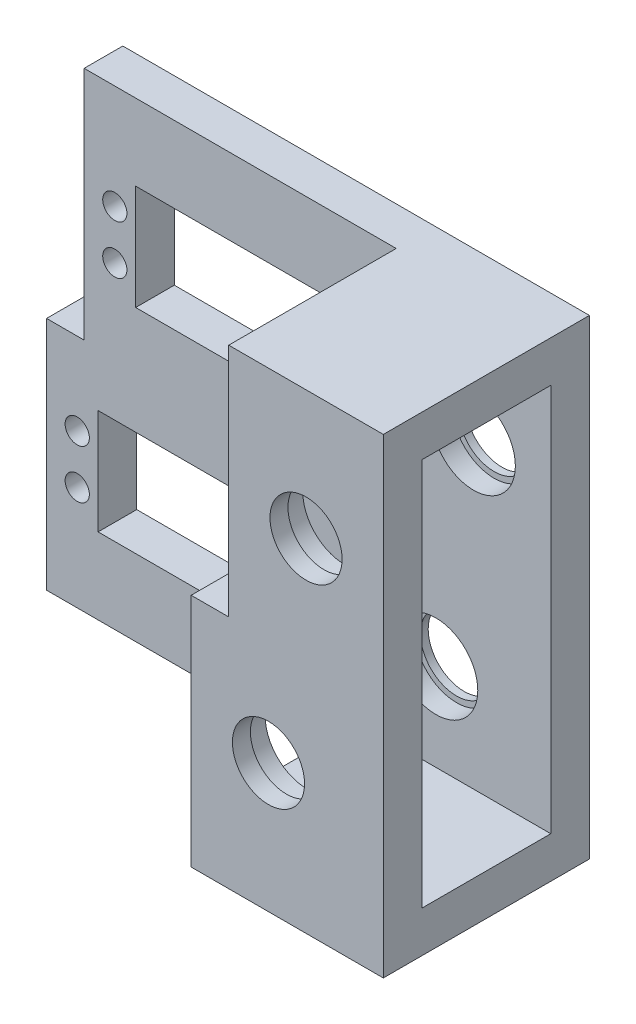
SolidWorks part; units mm, degrees
ref_plane "Front Plane" through (0, 0, 0) normal (0, 0, 1) x (1, 0, 0)
ref_plane "Top Plane" through (0, 0, 0) normal (0, 1, 0) x (1, 0, 0)
ref_plane "Right Plane" through (0, 0, 0) normal (1, 0, 0) x (0, 0, -1)
sketch "Sketch1" plane through (0, 0, 0) normal (0, 0, 1) x (1, 0, 0)
  line L0 (-15, 0) -> (22.2932, 0)
  line L5 (-15, 91.3619) -> (22.2932, 91.3619)
  line L6 (-15, 0) -> (-15, 91.3619)
  line L7 (22.2932, 0) -> (22.2932, 91.3619)
  line L8 (0, 25) -> (7.2932, 66.3619) construction
  line L9 (0, 25) -> (0, 79.2) construction
  circle A1 centre (0, 25) radius 8.125
  circle A2 centre (7.2932, 66.3619) radius 8.125
  point P0 (-15, 0)
  point P4 (0, 0)
  dimension "D2" = 16.25
  dimension "D5" = 25
  dimension "D4" = 15
  dimension "D6" = 25
  dimension "D8" = 42
  dimension "D9" = 10
  dimension "D10" = 15
extrude "Boss-Extrude1" add sketch "Sketch1" along normal blind 40
sketch "Sketch2" plane through (0, 0, 0) normal (0, 1, 0) x (1, 0, 0)
  line L1 (-15, -7.5) -> (22.2932, -7.5)
  line L2 (-15, -7.5) -> (-15, -32.5)
  line L3 (-15, -32.5) -> (22.2932, -32.5)
  line L4 (22.2932, -7.5) -> (22.2932, -32.5)
  line L6 (-15, -40) -> (-15, 0) construction
  line L7 (22.2932, -40) -> (22.2932, 0) construction
  point P4 (-15, -7.5)
  point P6 (22.2932, -32.5)
  point P8 (22.2932, -33.1865)
  point P9 (22.2932, -20)
  point P10 (22.2932, -20)
  point P12 (-15, -7.5)
  point P14 (-15, -7.5)
  point P15 (0, 0)
  point P17 (22.2932, -32.5)
  dimension "D1" = 25
extrude "Cut-Extrude1" cut sketch "Sketch2" along normal through all from offset 8
sketch "Sketch10" plane through (0, 0, 40) normal (0, 0, 1) x (1, 0, 0)
  circle A0 centre (7.2932, 66.3619) radius 8.125
  circle A1 centre (0, 25) radius 10.837
  circle A2 centre (7.2932, 66.3619) radius 7
  circle A3 centre (0, 25) radius 7
  circle A4 centre (7.2932, 66.3619) radius 8.125 construction
  circle A5 centre (0, 25) radius 8.125 construction
  dimension "D2" = 14
  dimension "D4" = 14
extrude "Boss-Extrude2" add sketch "Sketch10" against normal offset from surface (3.5 mm away) 4 up to face at (-8.125, 25, 32.5)
sketch "Sketch11" plane through (0, 0, 0) normal (0, 0, -1) x (-1, 0, 0)
  circle A0 centre (-7.2932, 66.3619) radius 8.125
  circle A1 centre (-7.2932, 66.3619) radius 7
  circle A2 centre (0, 25) radius 8.125
  circle A3 centre (0, 25) radius 7
  circle A4 centre (0, 25) radius 8.125 construction
  circle A5 centre (-7.2932, 66.3619) radius 8.125 construction
  dimension "D1" = 14
  dimension "D2" = 14
extrude "Boss-Extrude3" add sketch "Sketch11" against normal offset from surface (3.5 mm away) 4 up to face at (8.125, 25, 7.5)
ref_axis "Axis1" through (0, 25, 3.5) along (0, 0, -1)
ref_plane "Plane1" through (0, 25, 0) normal (0, -1, 0) x (-1, 0, 0)
ref_axis "Axis2" through (7.2932, 66.3619, 3.5) along (0, 0, -1)
ref_plane "Plane2" through (0, 66.3619, 0) normal (0, -1, 0) x (-1, 0, 0)
sketch "Sketch12" plane through (0, 0, 0) normal (0, 0, -1) x (-1, 0, 0)
  line L0 (-22, 25) -> (22, 25) construction
  line L1 (15, 0) -> (75.56, 0)
  line L2 (15, 0) -> (15, 91.3619)
  line L3 (15, 91.3619) -> (68.2668, 91.3619)
  line L5 (-22, 66.3619) -> (22, 66.3619) construction
  line L6 (24.66, 35.2) -> (65.56, 35.2)
  line L7 (24.66, 35.2) -> (24.66, 14.8)
  line L8 (24.66, 14.8) -> (65.56, 14.8)
  line L9 (65.56, 35.2) -> (65.56, 14.8)
  line L10 (-22.2932, 91.3619) -> (15, 91.3619) construction
  line L11 (17.3668, 76.5619) -> (58.2668, 76.5619)
  line L12 (17.3668, 76.5619) -> (17.3668, 56.1619)
  line L13 (17.3668, 56.1619) -> (58.2668, 56.1619)
  line L14 (58.2668, 76.5619) -> (58.2668, 56.1619)
  line L16 (15, 0) -> (-22.2932, 0) construction
  line L17 (15, 91.3619) -> (15, 0) construction
  line L18 (68.2668, 91.3619) -> (68.2668, 45.681)
  line L19 (68.2668, 45.681) -> (75.56, 45.681)
  line L20 (75.56, 45.681) -> (75.56, 0)
  line L21 (58.2668, 56.1619) -> (58.2668, 35.2) construction
  circle A0 centre (35, 25) radius 6.6 construction
  circle A1 centre (0, 25) radius 7 construction
  circle A2 centre (27.7068, 66.3619) radius 6.6 construction
  circle A3 centre (-7.2932, 66.3619) radius 7 construction
  point P15 (45.11, 14.8)
  point P16 (65.56, 25)
  point P17 (58.2668, 45.681)
  point P27 (17.3668, 66.3619)
  point P34 (37.8168, 56.1619)
  dimension "D7" = 13.2
  dimension "D11" = 13.2
  dimension "D2" = 20.4
  dimension "D3" = 40.9
  dimension "D4" = 10.11
  dimension "D9" = 10.11
  dimension "D5" = 35
  dimension "D6" = 10
  dimension "D8" = 10
extrude "Boss-Extrude4" add sketch "Sketch12" against normal up to surface (7.5 mm away) up to face at (8.125, 25, 7.5)
sketch "Sketch13" plane through (0, 0, 0) normal (0, 0, -1) x (-1, 0, 0)
  line L0 (24.66, 35.2) -> (24.66, 14.8) construction
  line L1 (-22, 25) -> (22, 25) construction
  line L2 (65.56, 14.8) -> (65.56, 35.2) construction
  line L3 (17.3668, 76.5619) -> (17.3668, 56.1619) construction
  line L5 (-22, 66.3619) -> (22, 66.3619) construction
  line L6 (58.2668, 56.1619) -> (58.2668, 76.5619) construction
  circle A0 centre (20.61, 29.75) radius 2.3495
  circle A1 centre (20.61, 20.25) radius 2.3495
  circle A2 centre (69.61, 29.75) radius 2.3495
  circle A3 centre (69.61, 20.25) radius 2.3495
  circle A4 centre (13.3168, 71.1119) radius 2.3495
  circle A5 centre (13.3168, 61.6119) radius 2.3495
  circle A6 centre (62.3168, 71.1119) radius 2.3495
  circle A7 centre (62.3168, 61.6119) radius 2.3495
  dimension "D1" = 4.699
  dimension "D2" = 4.05
  dimension "D3" = 9.5
  dimension "D4" = 4.75
  dimension "D5" = 4.05
  dimension "D7" = 9.5
  dimension "D8" = 4.05
  dimension "D9" = 4.75
  dimension "D10" = 4.05
extrude "Cut-Extrude2" cut sketch "Sketch13" against normal up to next
sketch "Sketch14" plane through (0, 0, 7.5) normal (0, 0, 1) x (1, 0, 0)
  line L0 (22.2932, 0) -> (22.2932, 91.3619) construction
  line L1 (22.2932, 91.3619) -> (-15, 91.3619)
  line L2 (22.2932, 91.3619) -> (22.2932, 83.3619)
  line L3 (22.2932, 83.3619) -> (-15, 83.3619)
  line L4 (-15, 91.3619) -> (-15, 83.3619)
  line L5 (22.2932, 91.3619) -> (-15, 91.3619) construction
  line L6 (-15, 91.3619) -> (-15, 0) construction
  dimension "D1" = 8
extrude "Boss-Extrude5" add sketch "Sketch14" along normal up to surface (25 mm away) up to face at (-8.125, 25, 32.5)
sketch "Sketch18" plane through (0, 0, 40) normal (0, 0, 1) x (1, 0, 0)
  line L0 (7.2932, 66.3619) -> (7.2932, 25) construction
  line L1 (-15, 91.3619) -> (-7.7068, 91.3619)
  line L2 (-15, 91.3619) -> (-15, 45.681)
  line L3 (-15, 45.681) -> (-7.7068, 45.681)
  line L4 (-7.7068, 91.3619) -> (-7.7068, 45.681)
  line L5 (0, 25) -> (7.2932, 25) construction
  circle A0 centre (7.2932, 66.3619) radius 8.125 construction
  point P11 (0, 0)
  point P13 (7.2932, 45.681)
  dimension "D1" = 15
extrude "Cut-Extrude4" cut sketch "Sketch18" against normal up to surface (32.5 mm away) up to face at (-10.9673, 71.1119, 7.5)
sketch "Sketch15" plane through (0, 0, 0) normal (0, 0, -1) x (-1, 0, 0)
  circle A0 centre (0, 25) radius 11
  circle A1 centre (-7.2932, 66.3619) radius 11
  dimension "D1" = 22
extrude "Cut-Extrude3" cut sketch "Sketch15" against normal blind 2
equation "\"D4@Sketch13\"=\"D3@Sketch13\"/2"
equation "\"D5@Sketch12\"=\"D1@Sketch12\""
equation "\"D8@Sketch13\"=\"D2@Sketch13\""
equation "\"D9@Sketch13\"=\"D7@Sketch13\"/2"
equation "\"D10@Sketch13\"=\"D5@Sketch13\""
